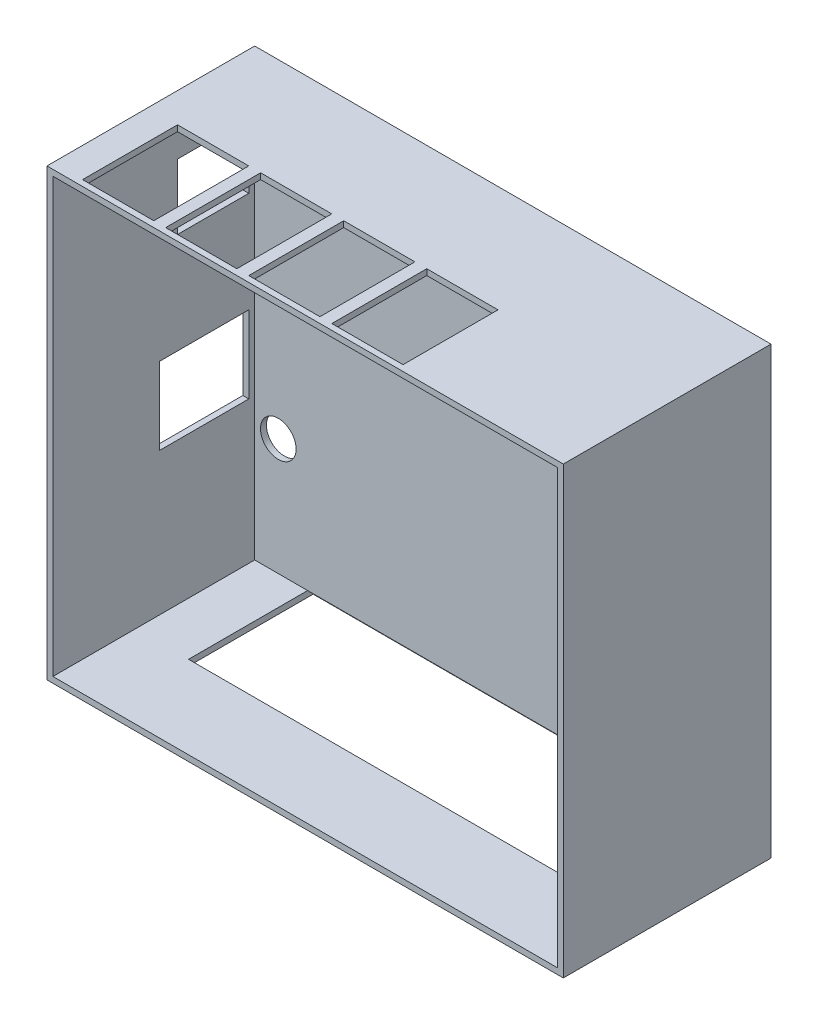
SolidWorks part; units mm, degrees
ref_plane "Plan de face" through (0, 0, 0) normal (0, 0, 1) x (1, 0, 0)
ref_plane "Plan de dessus" through (0, 0, 0) normal (0, 1, 0) x (1, 0, 0)
ref_plane "Plan de droite" through (0, 0, 0) normal (1, 0, 0) x (0, 0, -1)
sketch "Esquisse1" plane through (0, 0, 0) normal (0, 0, 1) x (1, 0, 0)
  line L1 (-132.205, 73) -> (-47.205, 73)
  line L2 (-132.205, 73) -> (-132.205, 0)
  line L3 (-132.205, 0) -> (-47.205, 0)
  line L4 (-47.205, 73) -> (-47.205, 0)
  dimension "D1" = 73
  dimension "D2" = 85
extrude "Boss.-Extru.2" add sketch "Esquisse1" along normal blind 1
sketch "Esquisse6" plane through (-47.205, 0, 0) normal (1, 0, 0) x (0, 0, -1)
  line L1 (0, 73) -> (-35, 73)
  line L2 (0, 73) -> (0, 0)
  line L3 (0, 0) -> (-35, 0)
  line L4 (-35, 73) -> (-35, 0)
  dimension "D1" = 73
  dimension "D2" = 35
extrude "Boss.-Extru.4" add sketch "Esquisse6" along normal blind 1
sketch "Esquisse8" plane through (-132.205, 0, 0) normal (-1, 0, 0) x (0, 0, 1)
  line L1 (0, 73) -> (35, 73)
  line L2 (0, 73) -> (0, 0)
  line L3 (0, 0) -> (35, 0)
  line L4 (35, 73) -> (35, 0)
extrude "Boss.-Extru.6" add sketch "Esquisse8" along normal blind 1
sketch "Esquisse10" plane through (-133.205, 0, 0) normal (-1, 0, 0) x (0, 0, 1)
  line L0 (0, 59.795) -> (2, 59.795) construction
  line L1 (2, 65) -> (14, 65)
  line L2 (2, 65) -> (2, 54)
  line L3 (2, 54) -> (14, 54)
  line L4 (14, 65) -> (14, 54)
  line L5 (0, 73) -> (0, 0) construction
  line L6 (8.5814, 73) -> (8.5814, 65) construction
  line L7 (35, 73) -> (0, 73) construction
  dimension "D1" = 11
  dimension "D2" = 12
extrude "Enlèv. mat.-Extru.1" cut sketch "Esquisse10" against normal blind 1
sketch "Esquisse11" plane through (-133.205, 0, 0) normal (-1, 0, 0) x (0, 0, 1)
  line L0 (11.1338, 0) -> (11.1338, 24) construction
  line L1 (17, 37) -> (2, 37)
  line L2 (17, 37) -> (17, 24)
  line L3 (17, 24) -> (2, 24)
  line L4 (2, 37) -> (2, 24)
  line L5 (0, 0) -> (35, 0) construction
  line L6 (2, 31.8249) -> (0, 31.8249) construction
  line L7 (0, 73) -> (0, 0) construction
  dimension "D1" = 15
  dimension "D2" = 13
extrude "Enlèv. mat.-Extru.2" cut sketch "Esquisse11" against normal blind 1
sketch "Esquisse13" plane through (0, 73, 0) normal (0, 1, 0) x (1, 0, 0)
  line L1 (-133.205, 0) -> (-46.205, 0)
  line L2 (-133.205, 0) -> (-133.205, -35)
  line L3 (-133.205, -35) -> (-46.205, -35)
  line L4 (-46.205, 0) -> (-46.205, -35)
  dimension "D1" = 35
  dimension "D2" = 87
extrude "Boss.-Extru.8" add sketch "Esquisse13" along normal blind 1
sketch "Esquisse14" plane through (0, 74, 0) normal (0, 1, 0) x (1, 0, 0)
  line L0 (-116.2799, -34) -> (-116.2799, -35) construction
  line L1 (-128.207, -18) -> (-116.207, -18)
  line L2 (-128.207, -18) -> (-128.207, -34)
  line L3 (-128.207, -34) -> (-116.207, -34)
  line L4 (-116.207, -18) -> (-116.207, -34)
  line L5 (-133.205, -35) -> (-46.205, -35) construction
  line L6 (-128.207, -21.7805) -> (-133.205, -21.7805) construction
  line L7 (-133.205, 0) -> (-133.205, -35) construction
  line L8 (-122.1939, -35) -> (-122.207, -34)
  line L9 (-123.3121, -18) -> (-123.3121, 0) construction
  line L10 (-46.205, 0) -> (-133.205, 0) construction
  dimension "D1" = 12
  dimension "D2" = 16
extrude "Enlèv. mat.-Extru.3" cut sketch "Esquisse14" against normal blind 1 contours L2 L1 L4 L3
sketch "Esquisse18" plane through (0, 74, 0) normal (0, 1, 0) x (1, 0, 0)
  line L1 (-114.207, -18) -> (-102.207, -18)
  line L2 (-114.207, -18) -> (-114.207, -34)
  line L3 (-114.207, -34) -> (-102.207, -34)
  line L4 (-102.207, -18) -> (-102.207, -34)
  line L6 (-108.207, -18) -> (-108.207, 0) construction
  line L7 (-46.205, 0) -> (-133.205, 0) construction
  line L8 (-116.207, -27.2223) -> (-114.207, -27.2223) construction
  line L9 (-116.207, -18) -> (-116.207, -34) construction
  dimension "D1" = 12
  dimension "D2" = 16
extrude "Enlèv. mat.-Extru.5" cut sketch "Esquisse18" against normal blind 1
sketch "Esquisse20" plane through (0, 74, 0) normal (0, 1, 0) x (1, 0, 0)
  line L0 (-94.6424, 0) -> (-94.6424, -18) construction
  line L1 (-100.207, -18) -> (-88.207, -18)
  line L2 (-100.207, -18) -> (-100.207, -34)
  line L3 (-100.207, -34) -> (-88.207, -34)
  line L4 (-88.207, -18) -> (-88.207, -34)
  line L5 (-46.205, 0) -> (-133.205, 0) construction
  line L6 (-100.207, -27.2382) -> (-102.207, -27.2382) construction
  line L7 (-102.207, -34) -> (-102.207, -18) construction
  dimension "D1" = 12
  dimension "D2" = 16
extrude "Enlèv. mat.-Extru.6" cut sketch "Esquisse20" against normal blind 1
sketch "Esquisse21" plane through (0, 74, 0) normal (0, 1, 0) x (1, 0, 0)
  line L0 (-81.659, 0) -> (-81.659, -18) construction
  line L1 (-86.207, -18) -> (-74.207, -18)
  line L2 (-86.207, -18) -> (-86.207, -34)
  line L3 (-86.207, -34) -> (-74.207, -34)
  line L4 (-74.207, -18) -> (-74.207, -34)
  line L5 (-46.205, 0) -> (-133.205, 0) construction
  line L6 (-86.207, -22.4048) -> (-88.207, -22.4048) construction
  line L7 (-88.207, -34) -> (-88.207, -18) construction
  dimension "D1" = 12
  dimension "D2" = 16
extrude "Enlèv. mat.-Extru.7" cut sketch "Esquisse21" against normal blind 1
sketch "Esquisse22" plane through (0, 0, 1) normal (0, 0, 1) x (1, 0, 0)
  circle A0 centre (-128.3346, 69.1704) radius 3
  point P2 (0, 0)
sketch "Esquisse23" plane through (0, 0, 1) normal (0, 0, 1) x (1, 0, 0)
  circle A0 centre (-128.2288, 19.6605) radius 3
  point P2 (0, 0)
sketch "Esquisse24" plane through (0, 0, 1) normal (0, 0, 1) x (1, 0, 0)
  line L0 (-73.2164, 69.223) -> (-74.2164, 69.223) construction
  circle A0 centre (-70.2164, 69.223) radius 3
  point P2 (0, 0)
  point P3 (0, 0)
  point P4 (0, 0)
  point P7 (0, 0)
  point P8 (0, 0)
sketch "Esquisse25" plane through (0, 0, 0) normal (0, -1, 0) x (1, 0, 0)
  line L1 (-133.205, 35) -> (-46.205, 35)
  line L2 (-133.205, 35) -> (-133.205, 0)
  line L3 (-133.205, 0) -> (-46.205, 0)
  line L4 (-46.205, 35) -> (-46.205, 0)
extrude "Boss.-Extru.11" add sketch "Esquisse25" along normal blind 1
sketch "Esquisse26" plane through (0, -1, 0) normal (0, -1, 0) x (1, 0, 0)
  line L1 (-123.286, 21.0671) -> (-46.286, 21.0671)
  line L2 (-123.286, 21.0671) -> (-123.286, 0.0671)
  line L3 (-123.286, 0.0671) -> (-46.286, 0.0671)
  line L4 (-46.286, 21.0671) -> (-46.286, 0.0671)
  dimension "D1" = 77
  dimension "D2" = 21
extrude "Enlèv. mat.-Extru.13" cut sketch "Esquisse26" against normal blind 1
extrude "Enlèv. mat.-Extru.14" cut sketch "Esquisse23" against normal blind 10
extrude "Enlèv. mat.-Extru.15" cut sketch "Esquisse22" against normal blind 10
extrude "Enlèv. mat.-Extru.18" cut sketch "Esquisse24" against normal blind 10 contours A0
